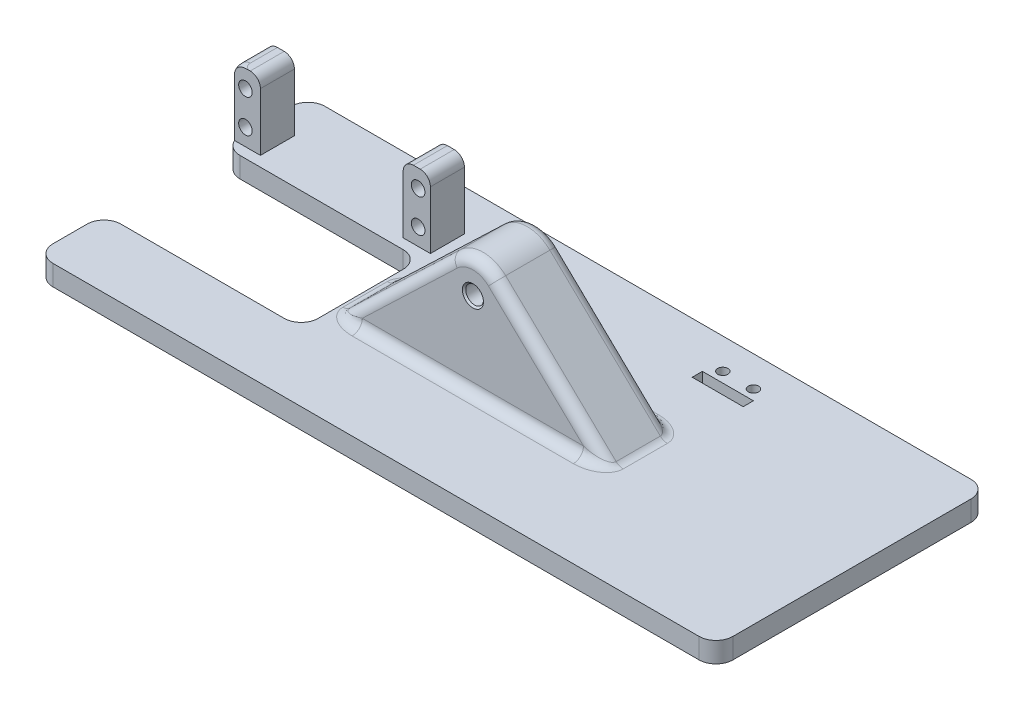
SolidWorks part; units mm, degrees
ref_plane "Front Plane" through (0, 0, 0) normal (0, 0, 1) x (1, 0, 0)
ref_plane "Top Plane" through (0, 0, 0) normal (0, 1, 0) x (1, 0, 0)
ref_plane "Right Plane" through (0, 0, 0) normal (1, 0, 0) x (0, 0, -1)
sketch "Sketch1" plane through (0, 0, 0) normal (0, 0, 1) x (1, 0, 0)
  line L0 (-6.6383, 6.9349) -> (-40, -25)
  line L1 (-40, -25) -> (40, -25)
  line L2 (40, -25) -> (6.6383, 6.9349)
  circle A0 centre (0, 0) radius 2.6
  arc A1 (6.6383, 6.9349) -> (-6.6383, 6.9349) centre (0, 0) ccw
  point P6 (0, -25)
  dimension "D1" = 5.2
  dimension "D2" = 7
  dimension "D3" = 80
  dimension "D4" = 25
extrude "Boss-Extrude1" add sketch "Sketch1" along normal blind 19
sketch "Sketch2" plane through (0, -25, 0) normal (0, -1, 0) x (-1, 0, 0)
  line L1 (-100, -47.5) -> (100, -47.5)
  line L2 (-100, -47.5) -> (-100, 32.5)
  line L3 (-100, 32.5) -> (100, 32.5)
  line L4 (100, -47.5) -> (100, 32.5)
  line L5 (40, -19) -> (-40, -19) construction
  point P9 (0, 32.5)
  dimension "D1" = 200
  dimension "D2" = 80
  dimension "D3" = 28.5
extrude "Boss-Extrude2" add sketch "Sketch2" along normal blind 6
chamfer "Chamfer1" distance 0.5 angle 45 2 edges at (2.6, 0, 19) (2.6, 0, 0)
sketch "Sketch4" plane through (0, 0, -32.5) normal (0, 0, -1) x (-1, 0, 0)
  line L0 (71, -25) -> (71, 2.2972) construction
  line L1 (100, -25) -> (92, -25)
  line L2 (100, -25) -> (100, -5)
  line L3 (100, -5) -> (92, -5)
  line L4 (92, -25) -> (92, -5)
  line L5 (100, -25) -> (-100, -25) construction
  line L6 (42, -25) -> (50, -25)
  line L7 (50, -25) -> (50, -5)
  line L8 (42, -5) -> (50, -5)
  line L9 (42, -25) -> (42, -5)
  circle A0 centre (96.4, -20) radius 2
  circle A1 centre (96.4, -10.2) radius 2
  circle A2 centre (45.6, -20) radius 2
  circle A3 centre (45.6, -10.2) radius 2
  dimension "D4" = 4
  dimension "D5" = 5
  dimension "D1" = 8
  dimension "D2" = 20
  dimension "D3" = 9.8
  dimension "D6" = 4.4
  dimension "D7" = 21
extrude "Boss-Extrude3" add sketch "Sketch4" along normal blind 10 from offset 22 offset against normal yes
sketch "Sketch5" plane through (0, -25, 0) normal (0, 1, 0) x (1, 0, 0)
  line L0 (-42, 20.5) -> (-42, 10.5) construction
  line L1 (-100, -27.5) -> (-42, -27.5)
  line L2 (-100, -27.5) -> (-100, 7.5)
  line L3 (-100, 7.5) -> (-42, 7.5)
  line L4 (-42, -27.5) -> (-42, 7.5)
  line L5 (100, -47.5) -> (-100, -47.5) construction
  line L6 (-100, -47.5) -> (-100, 10.5) construction
  line L7 (-100, 32.5) -> (100, 32.5) construction
  line L8 (100, 32.5) -> (100, -47.5) construction
  circle A0 centre (31, 23.5) radius 1.5
  circle A1 centre (40, 23.5) radius 1.5
  point P18 (0, 0)
  dimension "D5" = 3
  dimension "D1" = 35
  dimension "D2" = 20
  dimension "D3" = 0
  dimension "D4" = 9
  dimension "D6" = 9
  dimension "D7" = 60
extrude "Cut-Extrude2" cut sketch "Sketch5" against normal blind 7
fillet "Fillet1" radius 5 8 edges at (100, -28, -32.5) (100, -28, 47.5) (-100, -28, -32.5) (-100, -28, -7.5) (-42, -28, 27.5) (-42, -28, -7.5) (-100, -28, 47.5) (-100, -28, 27.5)
sketch "Sketch7" plane through (0, -25, 0) normal (0, 1, 0) x (1, 0, 0)
  line L1 (28, 20.5) -> (43, 20.5)
  line L2 (28, 20.5) -> (28, 17.5)
  line L3 (28, 17.5) -> (43, 17.5)
  line L4 (43, 20.5) -> (43, 17.5)
  circle A0 centre (31, 23.5) radius 1.5 construction
  circle A1 centre (40, 23.5) radius 1.5 construction
  dimension "D1" = 3
  dimension "D2" = 3
  dimension "D3" = 6
  dimension "D4" = 3
extrude "Cut-Extrude3" cut sketch "Sketch7" against normal blind 4
fillet "Fillet2" radius 3 15 edges at (-23.3192, -9.0326, 19) (0, 9.6, 19) (-23.3192, -9.0326, 0) (0, 9.6, 0) (-40, -25, 9.5) (23.3192, -9.0326, 19) (23.3192, -9.0326, 0) (-99.8945, -5, -11.4785) (-100, -5, -16.5) (-92, -5, -15.5) (-50, -5, -15.5) (-42, -5, -15.5) (40, -25, 9.5) (0, -25, 19) (0, -25, 0)
